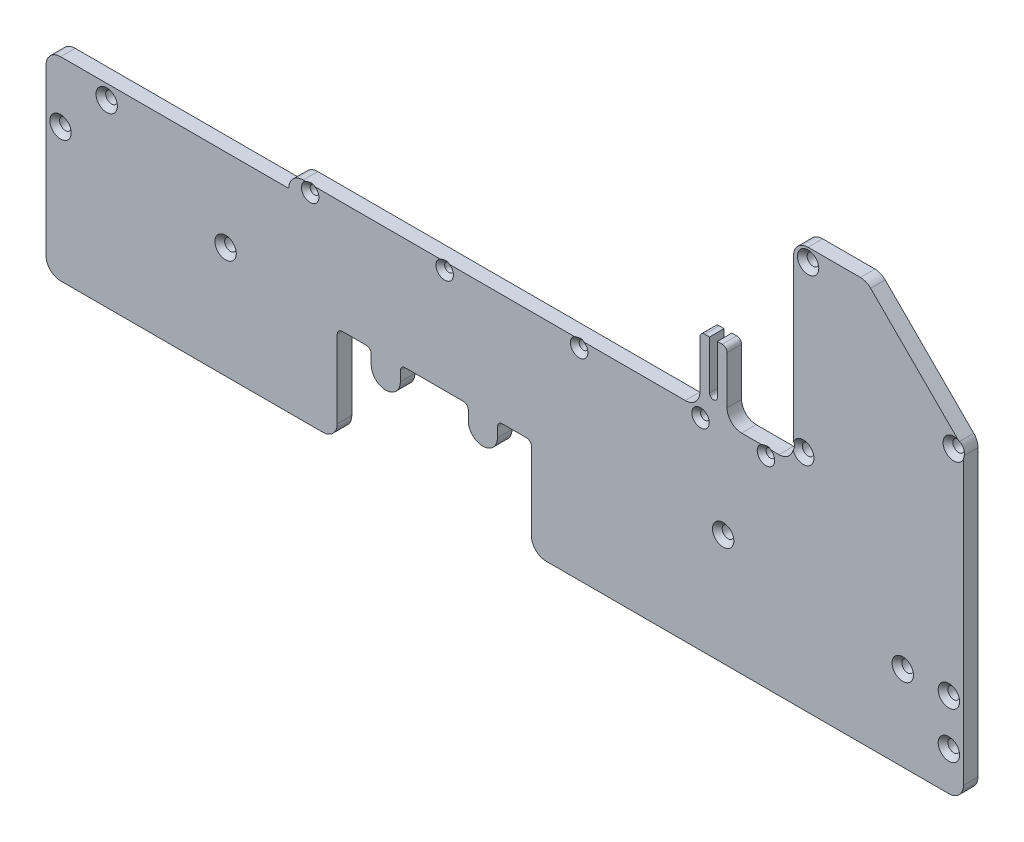
SolidWorks part; units mm, degrees
material "3.1355 (EN-AW 2024)"
ref_plane "Спереди" through (0, 0, 0) normal (0, 0, 1) x (1, 0, 0)
ref_plane "Сверху" through (0, 0, 0) normal (0, 1, 0) x (1, 0, 0)
ref_plane "Справа" through (0, 0, 0) normal (1, 0, 0) x (0, 0, -1)
sketch "Model" plane through (0, 0, 0) normal (0, 0, 1) x (1, 0, 0)
  line L1 (0, 20) -> (50, 20)
  line L2 (50, 20) -> (50, 23)
  line L11 (154, 23) -> (154, 0)
  line L19 (0, 0) -> (0, 20)
  line L54 (0, 0) -> (0, -20)
  line L55 (0, -20) -> (60, -20)
  line L56 (60, -20) -> (60, 0)
  line L57 (60, 0) -> (154, 0)
  line L60 (50, 23) -> (154, 23)
  dimension "D3" = 23
  dimension "D15" = 20
  dimension "D9" = 20
  dimension "D5" = 50
  dimension "D18" = 154
  dimension "D22" = 60
extrude "База" add sketch "Model" against normal blind 3
sketch "Эскиз14" plane through (0, 0, 0) normal (0, 0, 1) x (1, 0, 0)
  line L0 (60, 0) -> (154, 0) construction
  line L1 (67, 0) -> (73, 0)
  line L2 (67, 0) -> (67, -6)
  line L3 (67, -6) -> (73, -6)
  line L4 (73, 0) -> (73, -6)
  line L5 (60, -20) -> (60, 0) construction
  line L6 (87, 0) -> (93, 0)
  line L7 (87, 0) -> (87, -6)
  line L8 (87, -6) -> (93, -6)
  line L9 (93, 0) -> (93, -6)
  point P10 (70, -6)
  point P12 (90, -6)
  dimension "D1" = 6
  dimension "D2" = 10
  dimension "D3" = 20
extrude "Вставка в профиль 20*40" add sketch "Эскиз14" against normal up to surface (3 mm away) up to face at (66, 5.75, -3)
sketch "Эскиз15" plane through (0, 0, 0) normal (0, 0, 1) x (1, 0, 0)
  line L1 (0, 20) -> (0, -20) construction
  line L2 (154, 23) -> (50, 23) construction
  line L10 (134.7, 23) -> (134.7, 36.84)
  line L11 (134.7, 36.84) -> (136.7, 36.84)
  line L12 (136.7, 36.84) -> (136.7, 26.84)
  line L14 (138.3, 26.84) -> (138.3, 36.84)
  line L15 (138.3, 36.84) -> (140.3, 36.84)
  line L16 (140.3, 36.84) -> (140.3, 23)
  line L17 (140.3, 23) -> (134.7, 23)
  arc A0 (136.7, 26.84) -> (138.3, 26.84) centre (137.5, 26.84) ccw
  point P19 (137.5, 23)
  dimension "D1" = 5.6
  dimension "D2" = 1.6
  dimension "D3" = 137.5
  dimension "D4" = 36.84
  dimension "D5" = 10
extrude "Зажим датчика" add sketch "Эскиз15" against normal up to surface (3 mm away) up to face at (73, 1.375, -3)
sketch "Эскиз8" plane through (0, 0, 0) normal (0, 0, 1) x (1, 0, 0)
  line L0 (154, 23) -> (154, 63)
  line L1 (154, 63) -> (169, 63)
  line L2 (169, 63) -> (189, 43)
  line L3 (189, 43) -> (189, -20)
  line L6 (100, 0) -> (154, 0)
  line L7 (154, 0) -> (154, 23)
  line L8 (100, 0) -> (100, -20)
  line L12 (100, -20) -> (189, -20)
  line L13 (60, -20) -> (60, 0) construction
  dimension "D1" = 40
  dimension "D2" = 15
  dimension "D3" = 135
  dimension "D4" = 35
  dimension "D5" = 20
  dimension "D8" = 40
extrude "Панель управления" add sketch "Эскиз8" against normal up to surface (3 mm away) up to face at (94.5, 11.1767, -3)
fillet "Скругление5" radius 1 8 edges at (100, 0, -1.5) (93, 0, -1.5) (87, 0, -1.5) (73, 0, -1.5) (67, 0, -1.5) (60, 0, -1.5) (140.3, 36.84, -1.5) (134.7, 36.84, -1.5)
hole_wizard "Крепление M2" positions "Эскиз9" profile "Эскиз10" countersink size "M2" standard "DIN" end condition through all
sketch "Эскиз9" plane through (0, 0, 0) normal (0, 0, 1) x (1, 0, 0)
  point P0 (3, 7.5)
  point P3 (12.5, 17)
  point P18 (156, 25.95)
  point P27 (176.5, -2.5)
  point P30 (186, -12)
  point P33 (186, -2.5)
  point P36 (157, 60.32)
  point P40 (187, 42.08)
  dimension "D1" = 3
  dimension "D2" = 7.5
  dimension "D3" = 17
  dimension "D4" = 12.5
sketch "Эскиз10" plane through (3, 7.5, 0) normal (1, 0, 0) x (0, -1, 0)
  line L0 (0, 0) -> (0, 3)
  line L1 (0, 3) -> (1.2, 3)
  line L2 (1.2, 3) -> (1.2, 1)
  line L3 (1.2, 1) -> (2.2, 0)
  line L5 (2.2, 0) -> (0, 0)
  line L6 (-1.2, 1) -> (-2.2, 0) construction
  line L11 (0, -6.35) -> (0, 107.95) construction
  dimension "Диаметр сквозного отверстия" = 2.4
  dimension "Глубина сквозного отверстия" = 3
  dimension "Диаметр передней зенковки" = 4.4
  dimension "Угол передней зенковки" = 90
hole_wizard "Зенковка для винта M1.6" positions "Эскиз16" profile "Эскиз17" countersink size "M1.6" standard "DIN" end condition through all
sketch "Эскиз16" plane through (0, 0, 0) normal (0, 0, 1) x (1, 0, 0)
  line L0 (50, 20) -> (0, 20) construction
  point P0 (54.42, 21.5)
  point P3 (82.13, 21.5)
  point P6 (109.84, 21.5)
  point P9 (134.84, 21.5)
  point P12 (148.32, 21.5)
  dimension "D1" = 1.5
  dimension "D2" = 27.71
  dimension "D3" = 27.71
  dimension "D4" = 25
  dimension "D5" = 13.48
  dimension "D6" = 54.42
sketch "Эскиз17" plane through (54.42, 21.5, 0) normal (1, 0, 0) x (0, -1, 0)
  line L0 (0, 0) -> (0, 3)
  line L1 (0, 3) -> (0.9, 3)
  line L2 (0.9, 3) -> (0.9, 0.9)
  line L3 (0.9, 0.9) -> (1.8, 0)
  line L5 (1.8, 0) -> (0, 0)
  line L6 (-0.9, 0.9) -> (-1.8, 0) construction
  line L11 (0, -6.35) -> (0, 107.95) construction
  dimension "Диаметр сквозного отверстия" = 1.8
  dimension "Глубина сквозного отверстия" = 3
  dimension "Диаметр передней зенковки" = 3.6
  dimension "Угол передней зенковки" = 90
fillet "Скругление4" radius 3 12 edges at (0, 20, -1.5) (50, 23, -1.5) (154, 23, -1.5) (154, 63, -1.5) (169, 63, -1.5) (189, 43, -1.5) (140.3, 23, -1.5) (134.7, 23, -1.6467) (60, -20, -1.5) (189, -20, -1.5) (0, -20, -1.5) (100, -20, -1.5)
fillet "Скругление6" 2 edges at (67, -6, -1.5) (73, -6, -1.5) type full round first side face at (67, -3.5, -1.5) second side face at (73, -3.5, -1.5) middle face at (70, -6, -1.5)
fillet "Скругление7" 2 edges at (93, -6, -1.5) (87, -6, -1.5) type full round first side face at (93, -3.5, -1.5) second side face at (87, -3.5, -1.5) middle face at (90, -6, -1.5)
hole_wizard "УровеньПрижима-M2" positions "Эскиз18" profile "Эскиз19" countersink size "M2" standard "DIN" end condition through all
sketch "Эскиз18" plane through (0, 0, 0) normal (0, 0, 1) x (1, 0, 0)
  point P3 (37, 2.95)
  point P9 (139.5, 2.95)
  dimension "D1" = 102.5
  dimension "D3" = 2.95
  dimension "D4" = 37
sketch "Эскиз19" plane through (37, 2.95, 0) normal (1, 0, 0) x (0, -1, 0)
  line L0 (0, 0) -> (0, 3)
  line L1 (0, 3) -> (1.2, 3)
  line L2 (1.2, 3) -> (1.2, 1)
  line L3 (1.2, 1) -> (2.2, 0)
  line L5 (2.2, 0) -> (0, 0)
  line L6 (-1.2, 1) -> (-2.2, 0) construction
  line L11 (0, -6.35) -> (0, 107.95) construction
  dimension "Диаметр сквозного отверстия" = 2.4
  dimension "Глубина сквозного отверстия" = 3
  dimension "Диаметр передней зенковки" = 4.4
  dimension "Угол передней зенковки" = 90
